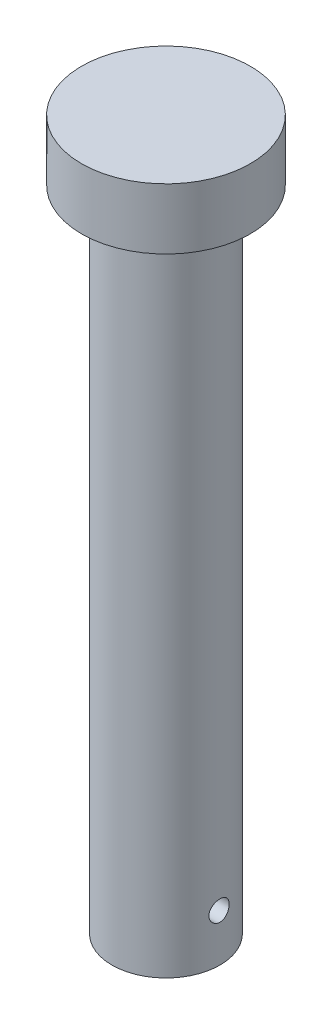
SolidWorks part; units mm, degrees
material "Gray Cast Iron"
ref_plane "Front Plane" through (0, 0, 0) normal (0, 0, 1) x (1, 0, 0)
ref_plane "Top Plane" through (0, 0, 0) normal (0, 1, 0) x (1, 0, 0)
ref_plane "Right Plane" through (0, 0, 0) normal (1, 0, 0) x (0, 0, -1)
sketch "Sketch1" plane through (0, 0, 0) normal (0, 1, 0) x (1, 0, 0)
  circle A0 centre (0, 0) radius 12.5
  circle A1 centre (0, 0) radius 8
  dimension "D1" = 25
  dimension "D2" = 16
extrude "Boss-Extrude1" add sketch "Sketch1" against normal blind 9 contours A1 | A0 A1 region at (-12.1464, 0, 0) region at (0, 0, 0)
extrude "Boss-Extrude2" add sketch "Sketch1<3>" against normal blind 96 from surface contours A1 region at (0, 0, 0) starting at face at (0, -9, 12.5)
sketch "Sketch1<3>" plane through (0, 0, 0) normal (0, 1, 0) x (1, 0, 0) same geometry as "Sketch1"
sketch "Sketch2" plane through (0, 0, 0) normal (1, 0, 0) x (0, 0, -1)
  line L0 (-12.5, -9) -> (12.5, -9) construction
  circle A0 centre (0, -98) radius 1.5
  dimension "D1" = 3
  dimension "D2" = 89
extrude "Cut-Extrude1" cut sketch "Sketch2" against normal mid plane 36
